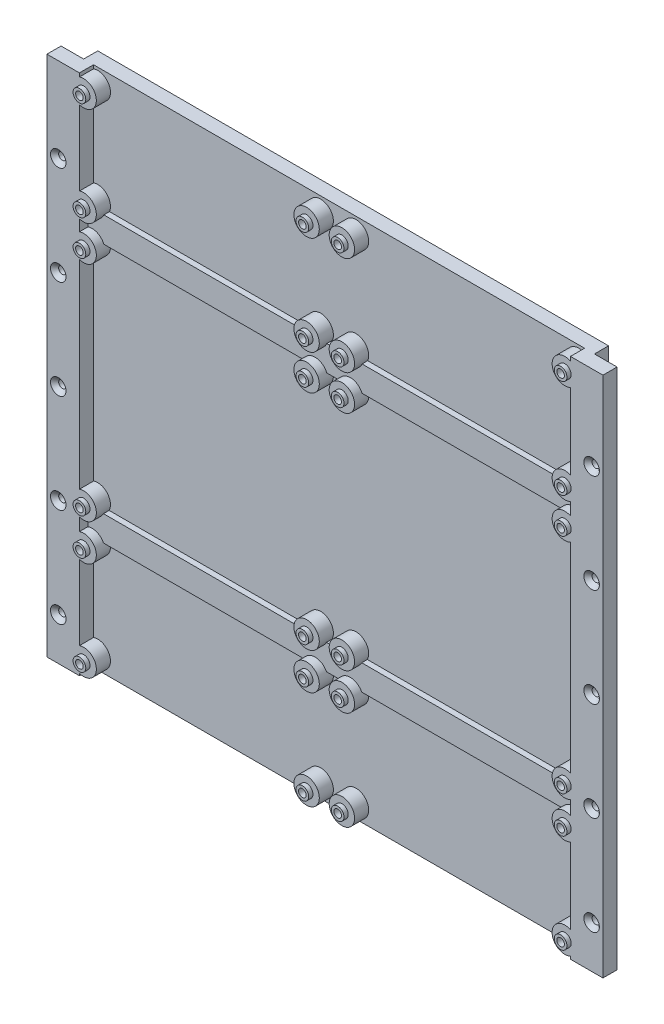
SolidWorks part; units mm, degrees
ref_plane "Plan de face" through (0, 0, 0) normal (0, 0, 1) x (1, 0, 0)
ref_plane "Plan de dessus" through (0, 0, 0) normal (0, 1, 0) x (1, 0, 0)
ref_plane "Plan de droite" through (0, 0, 0) normal (1, 0, 0) x (0, 0, -1)
sketch "Main - Sketch" plane through (0, 0, 0) normal (0, 0, 1) x (1, 0, 0)
  line L1 (-90.5, -92.5) -> (90.5, -92.5)
  line L2 (-90.5, -92.5) -> (-90.5, 92.5)
  line L3 (-90.5, 92.5) -> (90.5, 92.5)
  line L4 (90.5, -92.5) -> (90.5, 92.5)
  point P5 (0, 0)
  point P6 (0, -92.5)
  point P8 (-90.5, 0)
  dimension "D1" = 185
  dimension "D2" = 181
extrude "Main - Extrusion" add sketch "Main - Sketch" along normal blind 2.5
sketch "Horizontal Structure - Sketch" plane through (0, 0, 0) normal (0, 0, -1) x (-1, 0, 0)
  line L0 (90.5, -92.5) -> (-90.5, -92.5) construction
  line L1 (90.5, -87.5) -> (-90.5, -87.5)
  line L2 (90.5, -87.5) -> (90.5, -92.5)
  line L3 (90.5, -92.5) -> (-90.5, -92.5)
  line L4 (-90.5, -87.5) -> (-90.5, -92.5)
  point P4 (0, -92.5)
  point P7 (0, -92.5)
  dimension "D1" = 5
  dimension "D2" = 181
extrude "Horizontal Structure - Extrusion" add sketch "Horizontal Structure - Sketch" along normal blind 2.5
pattern_linear "Horizontal Structure - Linear Repeat" count 10 spacing 20 along (0, 1, 0) of "Horizontal Structure - Extrusion"
sketch "Vertical Structure - Sketch" plane through (0, 0, 0) normal (0, 0, -1) x (-1, 0, 0)
  line L1 (-90.5, -92.5) -> (-85.5, -92.5)
  line L2 (-90.5, -92.5) -> (-90.5, 92.5)
  line L3 (-90.5, 92.5) -> (-85.5, 92.5)
  line L4 (-85.5, -92.5) -> (-85.5, 92.5)
  line L5 (-90.5, 92.5) -> (90.5, 92.5) construction
  line L6 (90.5, -92.5) -> (-90.5, -92.5) construction
  line L7 (-90.5, 72.5) -> (-90.5, 87.5) construction
  point P4 (0, 0)
  dimension "D1" = 5
  dimension "D2" = 0
extrude "Vertical Structure - Extrusion" add sketch "Vertical Structure - Sketch" along normal blind 2.5
pattern_linear "Vertical Structure - Linear Repeat" count 9 spacing 22 along (-1, 0, 0) of "Vertical Structure - Extrusion"
sketch "Plot Base - Sketch" plane through (0, 0, 2.5) normal (0, 0, 1) x (1, 0, 0)
  line L0 (-90.5, -92.5) -> (90.5, -92.5) construction
  line L1 (-90.5, 92.5) -> (-90.5, -92.5) construction
  circle A0 centre (-85.5, -87.5) radius 4.5
  dimension "D1" = 9
  dimension "D2" = 5
  dimension "D3" = 5
extrude "Plot-Base - Extrusion" add sketch "Plot Base - Sketch" along normal blind 5
sketch "Plot Head - Sketch" plane through (0, 0, 7.5) normal (0, 0, 1) x (1, 0, 0)
  circle A0 centre (-85.5, -87.5) radius 2.25
  dimension "D1" = 4.5
extrude "Plot Head - Extrusion" add sketch "Plot Head - Sketch" along normal blind 1.5
sketch "Plot Head Hole Sketch" plane through (0, 0, 9) normal (0, 0, 1) x (1, 0, 0)
  circle A0 centre (-85.5, -87.5) radius 1.35
  dimension "D1" = 2.7
extrude "Plot Head Hole" cut sketch "Plot Head Hole Sketch" against normal through all
pattern_linear "Mechanical Board Board - First Vertical Linear Repeat" count 2 spacing 35 along (0, 1, 0) of "Plot-Base - Extrusion", "Plot Head - Extrusion", "Plot Head Hole"
pattern_linear "Mechanical Main Board - First Vertical Linear Repeat" count 2 spacing 48 along (0, 1, 0) of "Plot-Base - Extrusion", "Plot Head - Extrusion", "Plot Head Hole"
pattern_linear "Mechanical Main Board - Second Vertical Linear Repeat" count 2 spacing 127 along (0, 1, 0) of "Plot-Base - Extrusion", "Plot Head - Extrusion", "Plot Head Hole"
pattern_linear "Mechanical Motor Board - First Vertical Linear Repeat" count 2 spacing 139.5 along (0, 1, 0) of "Plot-Base - Extrusion", "Plot Head - Extrusion", "Plot Head Hole"
pattern_linear "Mechanical Motor Board - Second Vertical Linear Repeat" count 2 spacing 174.5 along (0, 1, 0) of "Plot-Base - Extrusion", "Plot Head - Extrusion", "Plot Head Hole"
pattern_linear "Range 2 - Linear Repeat" count 2 spacing 79 along (1, 0, 0) of "Mechanical Board Board - First Vertical Linear Repeat", "Mechanical Main Board - First Vertical Linear Repeat", "Mechanical Main Board - Second Vertical Linear Repeat", "Mechanical Motor Board - First Vertical Linear Repeat", "Mechanical Motor Board - Second Vertical Linear Repeat", "Plot-Base - Extrusion", "Plot Head - Extrusion", "Plot Head Hole"
pattern_linear "Range 3-4 - Linear Repeat" count 2 spacing 91.5 along (1, 0, 0) of "Range 2 - Linear Repeat", "Plot-Base - Extrusion", "Plot Head - Extrusion", "Plot Head Hole", "Mechanical Board Board - First Vertical Linear Repeat", "Mechanical Main Board - First Vertical Linear Repeat", "Mechanical Main Board - Second Vertical Linear Repeat", "Mechanical Motor Board - First Vertical Linear Repeat", "Mechanical Motor Board - Second Vertical Linear Repeat"
sketch "Fix - Sketch" plane through (0, 0, 2.5) normal (0, 0, 1) x (1, 0, 0)
  line L0 (90.5, 92.5) -> (-90.5, 92.5) construction
  line L1 (-87, -92.5) -> (-98.5, -92.5)
  line L2 (-87, -92.5) -> (-87, 92.5)
  line L3 (-87, 92.5) -> (-98.5, 92.5)
  line L4 (-98.5, -92.5) -> (-98.5, 92.5)
  line L5 (-90.5, -92.5) -> (90.5, -92.5) construction
  line L6 (-90.5, 92.5) -> (-90.5, -92.5) construction
  dimension "D1" = 3.5
  dimension "D2" = 8
extrude "Fix - Extrusion" add sketch "Fix - Sketch" along normal blind 5
hole_wizard "Fraisage pour vis à tête fraisée M31" positions "Esquisse10" profile "Esquisse9" countersink size "M3" standard "Ansi Metric" end condition through all
sketch "Esquisse10" plane through (0, 0, 7.5) normal (0, 0, 1) x (1, 0, 0)
  line L0 (-98.5, 92.5) -> (-98.5, -92.5) construction
  line L1 (-87, 92.5) -> (-98.5, 92.5) construction
  point P0 (-94.5, 62.5)
  point P7 (-144.8095, 223.9066)
  dimension "D1" = 4
  dimension "D2" = 30
sketch "Esquisse9" plane through (-94.5, 62.5, 7.5) normal (1, 0, 0) x (0, -1, 0)
  line L0 (0, 0) -> (0, 10)
  line L1 (0, 10) -> (1.3, 10)
  line L2 (1.3, 10) -> (1.3, 1.45)
  line L3 (1.3, 1.45) -> (2.75, 0)
  line L5 (2.75, 0) -> (0, 0)
  line L6 (-1.3, 1.45) -> (-2.75, 0) construction
  line L11 (0, -6.35) -> (0, 107.95) construction
  dimension "Diamètre du perçage jusqu'au prochain" = 2.6
  dimension "Profondeur du perçage jusqu'au prochain" = 10
  dimension "Diamètre du fraisage entrant" = 5.5
  dimension "Angle du fraisage entrant" = 90
pattern_linear "Répétition linéaire11" count 5 spacing 35 along (0, -1, 0) of "Fraisage pour vis à tête fraisée M31"
mirror "Symétrie1" about plane through (0, 0, 0) normal (1, 0, 0) of "Répétition linéaire11", "Fraisage pour vis à tête fraisée M31", "Fix - Extrusion"
sketch "Cross Plate 1" plane through (0, 0, 2.5) normal (0, 0, 1) x (1, 0, 0)
  line L0 (87, 43.5311) -> (87, 47.9689) construction
  line L1 (-87, 50.25) -> (87, 50.25)
  line L2 (-87, 50.25) -> (-87, 41.25)
  line L3 (-87, 41.25) -> (87, 41.25)
  line L4 (87, 50.25) -> (87, 41.25)
  line L5 (-87, 43.7426) -> (-87, 47.7574) construction
  point P6 (87, 45.75)
  point P7 (85.5, 46.7381)
  point P8 (0, 0)
  point P13 (0, 0)
  point P14 (0, 0)
  point P15 (0, 0)
  dimension "D1" = 9
extrude "Cross Plate 1 - Extrusion" add sketch "Cross Plate 1" along normal blind 2
sketch "Cross Plate 2 - Sketch" plane through (0, 0, 2.5) normal (0, 0, 1) x (1, 0, 0)
  line L0 (87, -48.4689) -> (87, -43.5311) construction
  line L1 (-87, -41.5) -> (87, -41.5)
  line L2 (-87, -41.5) -> (-87, -50.5)
  line L3 (-87, -50.5) -> (87, -50.5)
  line L4 (87, -41.5) -> (87, -50.5)
  line L5 (-87, -48.2574) -> (-87, -43.7426) construction
  point P4 (87, -46)
  point P5 (85.5, -46)
  point P8 (87, -46)
  dimension "D1" = 9
extrude "Cross Plate 2 - Extrusion" add sketch "Cross Plate 2 - Sketch" along normal blind 2
